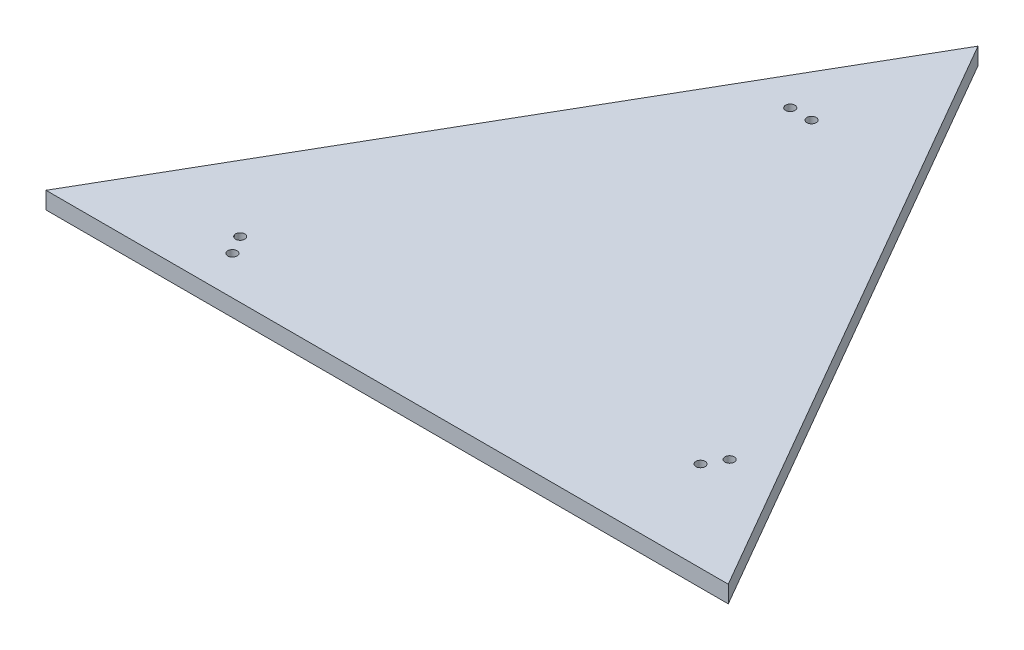
SolidWorks part; units mm, degrees
ref_plane "Front Plane" through (0, 0, 0) normal (0, 0, 1) x (1, 0, 0)
ref_plane "Top Plane" through (0, 0, 0) normal (0, 1, 0) x (1, 0, 0)
ref_plane "Right Plane" through (0, 0, 0) normal (1, 0, 0) x (0, 0, -1)
sketch "Sketch1" plane through (0, 0, 0) normal (0, 1, 0) x (1, 0, 0)
  line L1 (0, 146.647) -> (-127, -73.3235)
  line L2 (-127, -73.3235) -> (127, -73.3235)
  line L3 (127, -73.3235) -> (0, 146.647)
  circle A0 centre (0, 0) radius 73.3235 construction
  dimension "D1" = 254
extrude "Boss-Extrude1" add sketch "Sketch1" along normal blind 6.35
sketch "Sketch2" plane through (0, 6.35, 0) normal (0, 1, 0) x (1, 0, 0)
  line L0 (-127, -73.3235) -> (63.5, 36.6617) construction
  line L1 (127, -73.3235) -> (0, 146.647) construction
  line L2 (0, -73.3235) -> (0, 146.647) construction
  line L3 (-127, -73.3235) -> (127, -73.3235) construction
  line L5 (-63.5, 36.6617) -> (127, -73.3235) construction
  line L7 (0, 146.647) -> (-127, -73.3235) construction
  line L9 (0, -174.0988) -> (150.774, 87.0494)
  line L11 (150.774, 87.0494) -> (-150.774, 87.0494)
  line L12 (-150.774, 87.0494) -> (0, -174.0988)
  circle A0 centre (0, 0) radius 87.0494 construction
  line B0 (88.4014, -30.508) -> (79.5114, -45.9059) construction
  line B1 (84.277, -28.1268) -> (92.5259, -32.8893)
  line B2 (84.277, -28.1268) -> (75.387, -43.5247)
  line B3 (75.387, -43.5247) -> (83.6359, -48.2872)
  line B4 (92.5259, -32.8893) -> (83.6359, -48.2872)
  circle B5 centre (83.0801, -39.7248) radius 1.7272
  circle B6 centre (87.0425, -32.8617) radius 1.7272
  line B7 (-70.6214, -61.3039) -> (-79.5114, -45.9059) construction
  line B8 (-66.497, -58.9226) -> (-74.7459, -63.6851)
  line B9 (-66.497, -58.9226) -> (-75.387, -43.5247)
  line B10 (-75.387, -43.5247) -> (-83.6359, -48.2872)
  line B11 (-74.7459, -63.6851) -> (-83.6359, -48.2872)
  circle B12 centre (-75.9427, -52.0871) radius 1.7272
  circle B13 centre (-71.9803, -58.9502) radius 1.7272
  line B14 (-17.78, 91.8119) -> (0, 91.8119) construction
  line B15 (-17.78, 87.0494) -> (-17.78, 96.5744)
  line B16 (-17.78, 87.0494) -> (0, 87.0494)
  line B17 (0, 87.0494) -> (0, 96.5744)
  line B18 (-17.78, 96.5744) -> (0, 96.5744)
  circle B19 centre (-7.1374, 91.8119) radius 1.7272
  circle B20 centre (-15.0622, 91.8119) radius 1.7272
sketch_block_instance "Block1-4"
sketch_block "Block1" parameters "D3"=3.4544, "D1"=17.78, "D2"=9.525, "D4"=7.1374, "D5"=7.9248
sketch_block_instance "Block1-5"
sketch_block_instance "Block1-6"
extrude "Cut-Extrude1" cut sketch "Sketch2" against normal through all contours B12 | B13 | B5 | B20 | B19 | B6 region at (83.0801, 6.35, 39.7248) region at (-75.9427, 6.35, 52.0871) region at (-71.9803, 6.35, 58.9502) region at (-7.1374, 6.35, -91.8119) region at (-15.0622, 6.35, -91.8119)
